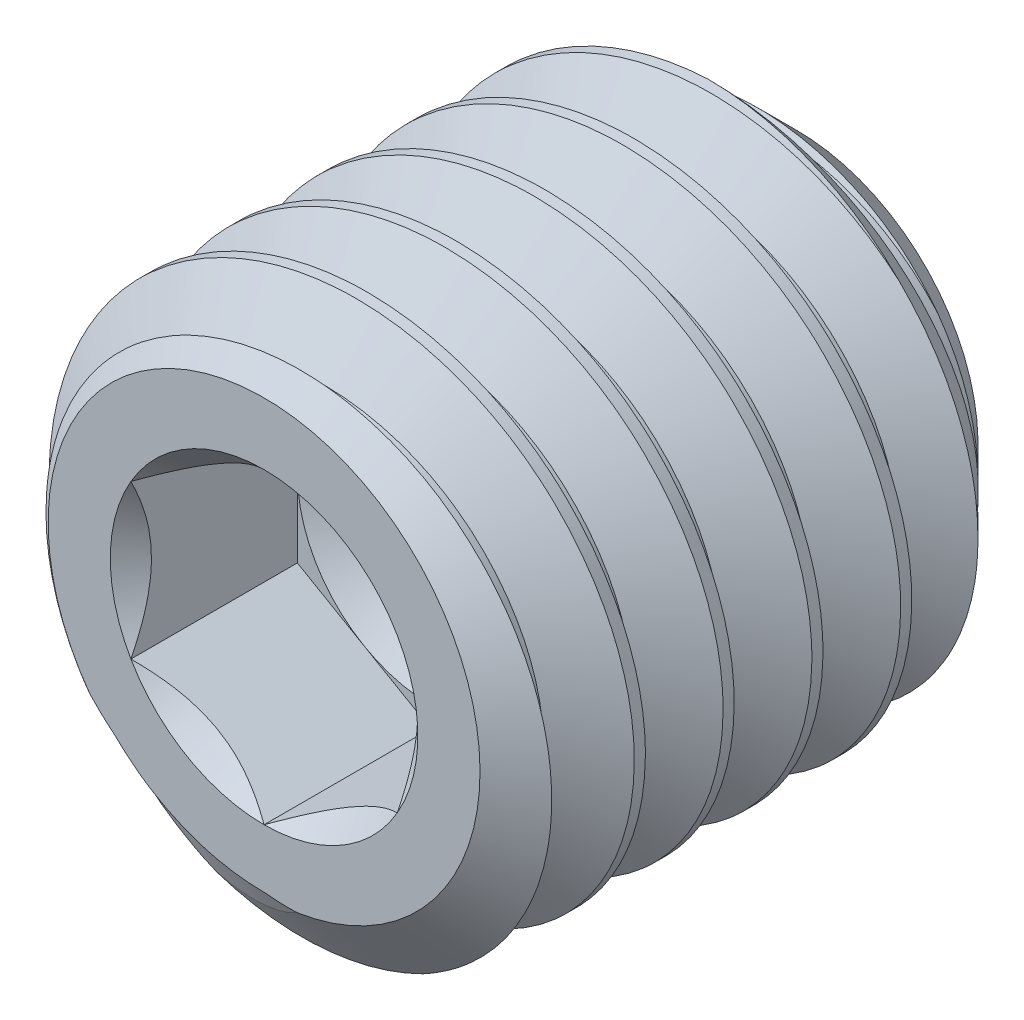
SolidWorks part; units mm, degrees
ref_plane "Front" through (0, 0, 0) normal (0, 0, 1) x (1, 0, 0)
ref_plane "Top" through (0, 0, 0) normal (0, 1, 0) x (1, 0, 0)
ref_plane "Right" through (0, 0, 0) normal (1, 0, 0) x (0, 0, -1)
sketch "Sketch22" plane through (0, 0, 0) normal (1, 0, 0) x (0, 0, -1)
  line L0 (-2.3812, 0) -> (-2.3812, 1.9304)
  line L1 (-2.3812, 1.9304) -> (-2.0433, 2.413)
  line L2 (-2.0433, 2.413) -> (1.5875, 2.413)
  line L3 (1.5875, 2.413) -> (2.3812, 1.6193)
  line L4 (-0.2279, 2.413) -> (-0.2279, -2.413) construction
  line L5 (2.3812, 0) -> (-2.3812, 0)
  line L7 (2.3812, 0) -> (2.3812, 1.6193)
  line L10 (-2.3812, 1.9304) -> (-2.3812, -1.9304) construction
  point P13 (-0.2279, 0)
  dimension "Length" = 4.7625
  dimension "D3" = 35
  dimension "D1" = 3.8608
  dimension "Dia" = 4.826
  dimension "D2" = 0.7937
  dimension "D4" = 45
revolve "Revolve1" add sketch "Sketch22" angle 360 about L5
ref_plane "Plane1" through (0, 0, -2.3812) normal (0, 0, 1) x (1, 0, 0)
sketch "Sketch27" plane through (0, 0, -2.3812) normal (0, 0, 1) x (1, 0, 0)
  circle A0 centre (0, 0) radius 2.413 construction
  circle A1 centre (0, 0) radius 2.413
curve "Helix/Spiral1" pitch 0.7937 height 5.5563 radius 2.413 centre (0, 0, -2.3812) axis (0, 0, 1) start towards (1, 0, 0)
sketch "Sketch28" plane through (0, 0, 0) normal (1, 0, 0) x (0, 0, -1)
  line L0 (2.3812, 2.413) -> (3.0758, 2.413)
  line L1 (3.0758, 2.413) -> (2.7781, 1.8974)
  line L2 (2.7781, 1.8974) -> (2.6789, 1.8974)
  line L3 (2.6789, 1.8974) -> (2.3812, 2.413)
  line L4 (2.5301, 2.1552) -> (2.927, 2.1552) construction
  line L6 (-2.0433, 2.413) -> (1.5875, 2.413) construction
  line L7 (2.3812, 2.6543) -> (2.3812, -2.6543) construction
  dimension "D3" = 60
  dimension "D2" = 0.3969
sweep "Cut-Sweep2" cut profiles "Sketch28" path "Helix/Spiral1" align with end faces yes
sketch "Sketch23" plane through (0, 0, 2.3812) normal (0, 0, 1) x (1, 0, 0)
  line L1 (0, 1.3748) -> (-1.1906, 0.6874)
  line L2 (-1.1906, 0.6874) -> (-1.1906, -0.6874)
  line L3 (-1.1906, -0.6874) -> (0, -1.3748)
  line L4 (0, -1.3748) -> (1.1906, -0.6874)
  line L5 (1.1906, -0.6874) -> (1.1906, 0.6874)
  line L6 (1.1906, 0.6874) -> (0, 1.3748)
  circle A0 centre (0, 0) radius 1.1906 construction
extrude "Cut-Extrude10" cut sketch "Sketch23" against normal blind 1.4883
sketch "Sketch24" plane through (0, 0, 2.3812) normal (0, 0, 1) x (1, 0, 0)
  circle A0 centre (0, 0) radius 1.3748
extrude "Cut-Extrude11" cut sketch "Sketch24" against normal through all draft 45
sketch "Sketch26" plane through (0, 0, 0.893) normal (0, 0, 1) x (1, 0, 0)
  circle A0 centre (0, 0) radius 1.1906 construction
  circle A1 centre (0, 0) radius 1.1906
extrude "Cut-Extrude12" cut sketch "Sketch26" against normal through all draft 60
sketch "Sketch30" plane through (0, 0, 0) normal (1, 0, 0) x (0, 0, -1)
  line L0 (-2.0433, 2.413) -> (1.5875, 2.413) construction
  line L1 (-2.3812, 0) -> (-2.3812, 1.9304) construction
  line L2 (2.3812, 0) -> (2.3812, 1.6193) construction
  point P0 (-2.3812, 2.413)
  point P1 (2.3812, 2.413)
  point P2 (2.3812, -2.413)
  point P11 (0.3969, -2.413)
  dimension "D1" = 1.9844
equation "\"D1@Sketch28\" = \"D4@Helix/Spiral1\" * .125"
equation "\"D3@Helix/Spiral1\" = \"Length@Sketch22\" + \"D4@Helix/Spiral1\""
equation "\"D1@Sketch30\" = \"D4@Helix/Spiral1\" * 2.5"
equation "\"hex Depth@Cut-Extrude10\" = \"Hex@Sketch23\" * .625"
equation "\"D2@Sketch28\" = \"D4@Helix/Spiral1\" * .5"
equation "\"D1@Sketch22\" = \"Dia@Sketch22\" * .8"
equation "\"D2@Sketch22\" = \"D4@Helix/Spiral1\""
